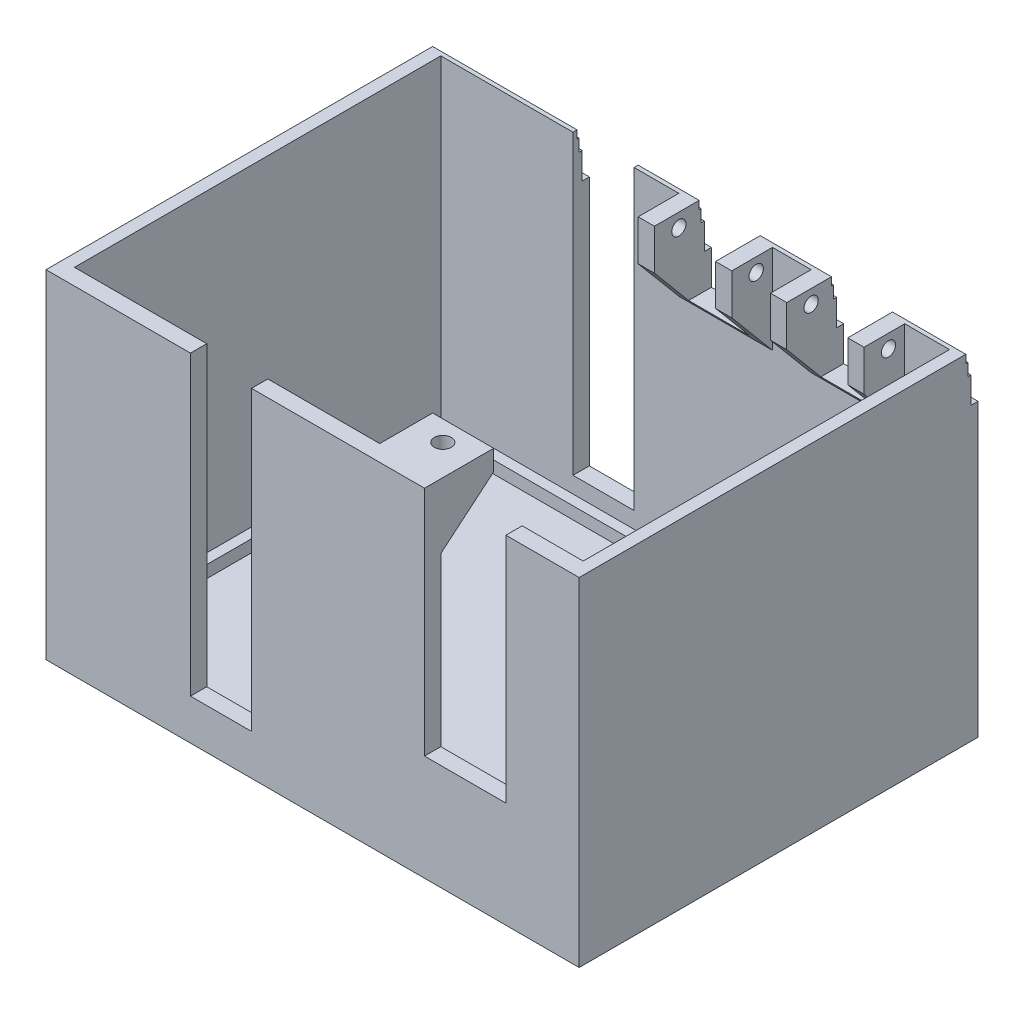
SolidWorks part; units mm, degrees
ref_plane "Front Plane" through (0, 0, 0) normal (0, 0, 1) x (1, 0, 0)
ref_plane "Top Plane" through (0, 0, 0) normal (0, 1, 0) x (1, 0, 0)
ref_plane "Right Plane" through (0, 0, 0) normal (1, 0, 0) x (0, 0, -1)
sketch "Sketch1" plane through (0, 0, 0) normal (0, 1, 0) x (1, 0, 0)
  line L1 (62.5, -45) -> (-62.5, -45)
  line L2 (62.5, -45) -> (62.5, 45)
  line L3 (62.5, 45) -> (-62.5, 45)
  line L4 (-62.5, -45) -> (-62.5, 45)
  line L5 (62.5, -45) -> (-62.5, 45) construction
  line L6 (62.5, 45) -> (-62.5, -45) construction
  line L7 (65.5, -49) -> (-65.5, -49)
  line L8 (65.5, -49) -> (65.5, 49)
  line L9 (65.5, 49) -> (-65.5, 49)
  line L10 (-65.5, -49) -> (-65.5, 49)
  line L11 (65.5, -49) -> (-65.5, 49) construction
  line L12 (65.5, 49) -> (-65.5, -49) construction
  point P0 (0, 0)
  point P5 (0, 0)
  dimension "D4" = 4
  dimension "D1" = 125
  dimension "D2" = 90
  dimension "D3" = 3
extrude "Boss-Extrude1" add sketch "Sketch1" along normal blind 80
sketch "Sketch2" plane through (0, 0, 0) normal (0, -1, 0) x (1, 0, 0)
  line L1 (65.5, -49) -> (-65.5, -49)
  line L2 (65.5, -49) -> (65.5, 49)
  line L3 (65.5, 49) -> (-65.5, 49)
  line L4 (-65.5, -49) -> (-65.5, 49)
extrude "Boss-Extrude2" add sketch "Sketch2" along normal blind 3
sketch "Sketch4" plane through (0, 0, 0) normal (0, 1, 0) x (1, 0, 0)
  line L1 (-62.5, 45) -> (62.5, 45)
  line L2 (-62.5, 45) -> (-62.5, -45)
  line L3 (-62.5, -45) -> (62.5, -45)
  line L4 (62.5, 45) -> (62.5, -45)
  line L5 (59.5, -42) -> (-60, -42)
  line L6 (59.5, -42) -> (59.5, 42.5)
  line L7 (59.5, 42.5) -> (-60, 42.5)
  line L8 (-60, -42) -> (-60, 42.5)
  dimension "D1" = 2.5
  dimension "D2" = 2.5
  dimension "D3" = 3
  dimension "D4" = 3
extrude "Boss-Extrude3" add sketch "Sketch4" along normal blind 3
sketch "Sketch5" plane through (0, 0, -49) normal (0, 0, -1) x (-1, 0, 0)
  line L0 (-65.5, 80) -> (65.5, 80) construction
  line L1 (15, 80) -> (30, 80)
  line L2 (15, 80) -> (15, 7)
  line L3 (15, 7) -> (30, 7)
  line L4 (30, 80) -> (30, 7)
  line L5 (15, 80) -> (30, 7) construction
  line L6 (15, 7) -> (30, 80) construction
  line L7 (62.5, 74.3372) -> (62.5, 12.8298) construction
  line L8 (65.5, 80) -> (65.5, -3) construction
  line L9 (65.5, -3) -> (-65.5, -3) construction
  point P0 (22.5, 43.5)
  dimension "D1" = 3
  dimension "D2" = 40
  dimension "D3" = 15
  dimension "D4" = 10
extrude "Cut-Extrude1" cut sketch "Sketch5" against normal through all
sketch "Sketch6" plane through (0, 0, 45) normal (0, 0, -1) x (-1, 0, 0)
  line L0 (15, 80) -> (-62.5, 80) construction
  line L1 (-27.5, 23) -> (-47.5, 23)
  line L2 (-27.5, 23) -> (-27.5, 80)
  line L3 (-27.5, 80) -> (-47.5, 80)
  line L4 (-47.5, 23) -> (-47.5, 80)
  line L5 (-27.5, 23) -> (-47.5, 80) construction
  line L6 (-27.5, 80) -> (-47.5, 23) construction
  line L7 (62.5, 3) -> (-62.5, 3) construction
  line L8 (-62.5, 80) -> (-62.5, 3) construction
  point P0 (-37.5, 51.5)
  dimension "D1" = 20
  dimension "D2" = 20
  dimension "D3" = 25
extrude "Cut-Extrude2" cut sketch "Sketch6" against normal up to next
sketch "Sketch7" plane through (0, 0, -45) normal (0, 0, 1) x (1, 0, 0)
  line L0 (62.5, 80) -> (-15, 80) construction
  line L1 (32.5, 80) -> (47.5, 80)
  line L2 (32.5, 80) -> (32.5, 60)
  line L3 (32.5, 60) -> (47.5, 60)
  line L4 (47.5, 80) -> (47.5, 60)
  line L5 (65.5, 80) -> (65.5, -3) construction
  line L6 (0, 80) -> (15, 80)
  line L7 (0, 80) -> (0, 60)
  line L8 (0, 60) -> (15, 60)
  line L9 (15, 80) -> (15, 60)
  dimension "D1" = 20
  dimension "D2" = 18
  dimension "D3" = 15
  dimension "D4" = 15
  dimension "D5" = 17.5
extrude "Cut-Extrude3" cut sketch "Sketch7" against normal up to next
sketch "Sketch8" plane through (0, 0, -45) normal (0, 0, 1) x (1, 0, 0)
  line L1 (0, 80) -> (-4, 80)
  line L2 (0, 80) -> (0, 70)
  line L3 (0, 70) -> (-4, 70)
  line L4 (-4, 80) -> (-4, 70)
  line L5 (15, 80) -> (19, 80)
  line L6 (15, 80) -> (15, 70)
  line L7 (15, 70) -> (19, 70)
  line L8 (19, 80) -> (19, 70)
  line L9 (32.5, 80) -> (28.5, 80)
  line L10 (32.5, 80) -> (32.5, 70)
  line L11 (32.5, 70) -> (28.5, 70)
  line L12 (28.5, 80) -> (28.5, 70)
  line L13 (47.5, 80) -> (51.5, 80)
  line L14 (47.5, 80) -> (47.5, 70)
  line L15 (47.5, 70) -> (51.5, 70)
  line L16 (51.5, 80) -> (51.5, 70)
  dimension "D1" = 4
  dimension "D2" = 4
  dimension "D3" = 10
  dimension "D4" = 4
  dimension "D5" = 4
extrude "Boss-Extrude4" add sketch "Sketch8" along normal blind 10
sketch "Skizze2" plane through (-4, 0, 0) normal (-1, 0, 0) x (0, 0, 1)
  line L0 (-35, 70) -> (-45, 70)
  line L1 (-45, 70) -> (-45, 58.0825)
  line L2 (-45, 58.0825) -> (-35, 70)
  dimension "D1" = 40
extrude "3D Printer Support" add sketch "Skizze2" against normal up to vertex (55.5 mm away) up to point (51.5, 70, -35)
sketch "Skizze3" plane through (0, 0, -45) normal (0, 0, -1) x (-1, 0, 0)
  line L1 (-32.5, 70) -> (-47.5, 70)
  line L2 (-32.5, 70) -> (-32.5, 60)
  line L3 (-32.5, 60) -> (-47.5, 60)
  line L4 (-47.5, 70) -> (-47.5, 60)
  line L5 (-15, 60) -> (0, 60)
  line L6 (-15, 60) -> (-15, 70)
  line L7 (-15, 70) -> (0, 70)
  line L8 (0, 60) -> (0, 70)
extrude "Schnitt-Linear austragen1" cut sketch "Skizze3" against normal blind 20
sketch "Skizze4" plane through (0, 70, 0) normal (0, 1, 0) x (1, 0, 0)
  line L1 (28.5, 45) -> (19, 45)
  line L2 (28.5, 45) -> (28.5, 35)
  line L3 (28.5, 35) -> (19, 35)
  line L4 (19, 45) -> (19, 35)
extrude "Schnitt-Linear austragen2" cut sketch "Skizze4" against normal blind 20
sketch "Skizze5" plane through (-4, 0, 0) normal (-1, 0, 0) x (0, 0, 1)
  line L1 (-35, 80) -> (-45, 80) construction
  line L2 (-49, 60) -> (-49, 80) construction
  circle A0 centre (-41, 76.6459) radius 1.75
  point P5 (-40, 80)
  dimension "D3" = 3.5
  dimension "D1" = 8
  dimension "D2" = 3.5
extrude "Schnitt-Linear austragen3" cut sketch "Skizze5" against normal up to surface (55.5 mm away) up to face at (51.5, 72.0206, -40)
ref_plane "Ebene1" through (27.5, 0, 0) normal (1, 0, 0) x (0, 0, -1)
sketch "Skizze9" plane through (27.5, 0, 0) normal (1, 0, 0) x (0, 0, -1)
  line L0 (-45, 80) -> (-32, 80)
  line L1 (-32, 80) -> (-32, 75)
  line L2 (-32, 75) -> (-45, 64.0917)
  line L3 (-45, 64.0917) -> (-45, 80)
  line L4 (-45, 23) -> (-45, 80) construction
  line L5 (-49, 80) -> (-45, 80) construction
  line L6 (-39, 80) -> (-39, 58.0539) construction
  line L7 (-42.2981, 66) -> (6.0171, 66) construction
  dimension "D1" = 13
  dimension "D2" = 50
  dimension "D3" = 5
  dimension "D4" = 14
  dimension "D5" = 6
extrude "Aufsatz-Linear austragen2" add sketch "Skizze9" against normal blind 15
sketch "Skizze10" plane through (0, 80, 0) normal (0, 1, 0) x (1, 0, 0)
  line L0 (27.5, -49) -> (27.5, -32) construction
  line L1 (12.5, -45) -> (27.5, -45) construction
  line L2 (65.5, -49) -> (65.5, 49) construction
  circle A0 centre (20, -37) radius 2.1
  dimension "D1" = 4.2
  dimension "D2" = 8
  dimension "D3" = 7.5
  dimension "D4" = 45.5
extrude "Schnitt-Linear austragen4" cut sketch "Skizze10" against normal up to vertex (15.9083 mm away) up to point (12.5, 64.0917, 45)
sketch "Sketch9" plane through (-65.5, 0, 0) normal (-1, 0, 0) x (0, 0, 1)
  line L0 (-46, 78) -> (-46.5, 78)
  line L1 (-49, 80) -> (-46, 80)
  line L2 (-49, 68.5) -> (-49, 80)
  line L3 (-47.25, 75) -> (-47.25, 68.5)
  line L4 (-46, 80) -> (-46, 78)
  line L5 (-47.25, 68.5) -> (-49, 68.5)
  line L6 (-49, 80) -> (-49, -3) construction
  line L7 (-46.5, 78) -> (-46.5, 75)
  line L8 (-46.5, 75) -> (-47.25, 75)
  dimension "D1" = 1.75
  dimension "D2" = 2
  dimension "D3" = 6.5
  dimension "D4" = 3
  dimension "D5" = 0.5
  dimension "D6" = 3
extrude "Cut-Extrude4" cut sketch "Sketch9" against normal up to surface (131 mm away) up to face at (65.5, 38.5, 0)
